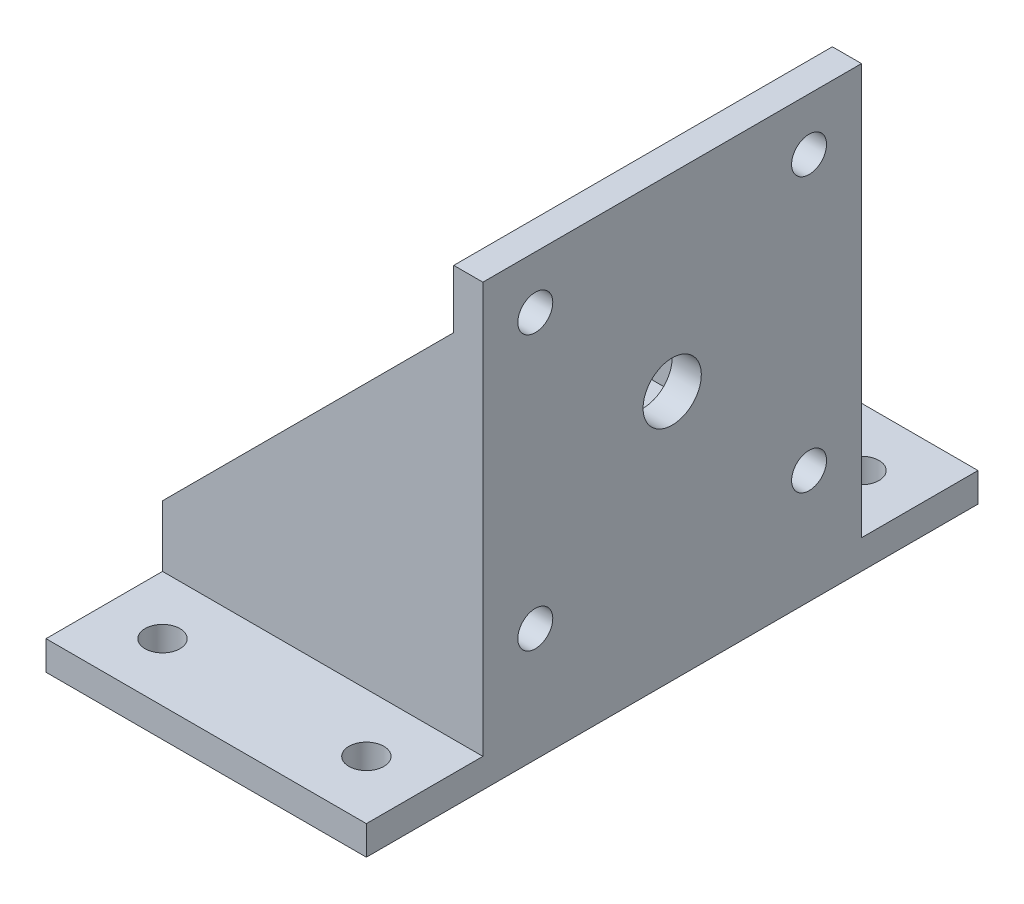
SolidWorks part; units mm, degrees
ref_plane "Front Plane" through (0, 0, 0) normal (0, 0, 1) x (1, 0, 0)
ref_plane "Top Plane" through (0, 0, 0) normal (0, 1, 0) x (1, 0, 0)
ref_plane "Right Plane" through (0, 0, 0) normal (1, 0, 0) x (0, 0, -1)
sketch "Sketch1" plane through (0, 0, 0) normal (0, 0, 1) x (1, 0, 0)
  line L0 (0, 0) -> (0, 60)
  line L1 (0, 60) -> (5, 60)
  line L2 (5, 60) -> (5, -15.5)
  line L3 (5, -15.5) -> (-50, -15.5)
  line L4 (-50, -15.5) -> (-50, 0)
  line L5 (-50, 0) -> (0, 0)
  dimension "D1" = 5
  dimension "D2" = 60
  dimension "D3" = 15.5
  dimension "D4" = 50
extrude "Boss-Extrude1" add sketch "Sketch1" along normal blind 65
sketch "Sketch2" plane through (0, 0, 0) normal (0, 0, -1) x (-1, 0, 0)
  line L0 (50, 0) -> (0, 50)
  line L6 (50, 0) -> (0, 0)
  line L7 (0, 0) -> (0, 60)
  line L8 (0, 60) -> (-5, 60)
  line L9 (-5, 60) -> (-5, -15.5)
  line L10 (-5, -15.5) -> (50, -15.5)
  line L11 (50, -15.5) -> (50, 0)
  line L12 (50, 0) -> (0, 0)
  line L13 (0, 0) -> (0, 60)
  line L14 (0, 60) -> (-5, 60)
  line L15 (-5, 60) -> (-5, -15.5)
  line L16 (-5, -15.5) -> (50, -15.5)
  line L17 (50, -15.5) -> (50, 0)
  line M8 (50, 0) -> (0, 0)
  line M9 (0, 0) -> (0, 60)
  dimension "D2" = 45
  dimension "D1" = 0
extrude "Boss-Extrude2" add sketch "Sketch2" against normal blind 5 contours M9 M8 region at (-16.6667, 16.6667, 0)
sketch "Sketch3" plane through (0, 0, 65) normal (0, 0, 1) x (1, 0, 0)
  line L3 (0, 50) -> (-50, 0)
  line L4 (-50, 0) -> (0, 0)
  line L5 (0, 0) -> (0, 50)
  line L7 (-50, 0) -> (0, 0)
  line L8 (0, 0) -> (0, 50)
  line L9 (0, 50) -> (-50, 0)
  dimension "D1" = 0
extrude "Boss-Extrude3" add sketch "Sketch3" against normal blind 5
sketch "Sketch4" plane through (0, 0, 0) normal (-1, 0, 0) x (0, 0, 1)
  line L0 (32.5, 60) -> (32.5, 0)
  line L2 (9, 4) -> (56, 4)
  line L3 (9, 4) -> (9, 51)
  line L4 (5, 0) -> (60, 0)
  line L5 (60, 0) -> (60, 50)
  line L6 (65, 60) -> (0, 60)
  line L7 (60, 50) -> (65, 50)
  line L8 (5, 0) -> (60, 0)
  line L9 (60, 0) -> (60, 50)
  line L10 (65, 60) -> (0, 60)
  line L12 (9, 51) -> (56, 51)
  line L13 (56, 4) -> (56, 51)
  line L14 (9, 4) -> (56, 51) construction
  line L15 (60, 50) -> (65, 50)
  line L16 (65, 50) -> (65, 60)
  line L17 (65, 50) -> (65, 60)
  line L18 (0, 60) -> (0, 50)
  line L19 (0, 60) -> (0, 50)
  line L20 (9, 51) -> (56, 4) construction
  line L22 (5, 50) -> (5, 0)
  line L23 (5, 50) -> (5, 0)
  line L24 (0, 50) -> (5, 50)
  line L25 (0, 50) -> (5, 50)
  circle A0 centre (32.5, 27.5) radius 5
  circle A1 centre (9, 51) radius 3
  circle A2 centre (56, 51) radius 3
  circle A3 centre (56, 4) radius 3
  circle A4 centre (9, 4) radius 3
  dimension "D2" = 10
  dimension "D4" = 6
  dimension "D3" = 47
  dimension "D5" = 27.5
  dimension "D1" = 0
extrude "Cut-Extrude1" cut sketch "Sketch4" against normal through all contours A0 | A1 | A2 | A3 | A4
sketch "Sketch5" plane through (0, -15.5, 0) normal (0, -1, 0) x (1, 0, 0)
  line L0 (-50, -20) -> (5, -20)
  line L1 (5, 85) -> (-50, 85)
  line L4 (-50, 0) -> (5, 0)
  line L5 (5, 0) -> (5, 65)
  line L6 (5, 65) -> (-50, 65)
  line L7 (-50, 65) -> (-50, 0)
  line L8 (-50, 0) -> (5, 0)
  line L9 (5, -20) -> (5, 85)
  line L10 (5, 65) -> (-50, 65)
  line L11 (-50, 85) -> (-50, -20)
  line M5 (-50, 0) -> (5, 0)
  line M7 (5, 65) -> (-50, 65)
  dimension "D1" = 0
  dimension "D2" = 20
  dimension "D3" = 20
extrude "Boss-Extrude4" add sketch "Sketch5" against normal blind 5 contours L11 L0 L9 M5 | L1 L11 L9 M7 region at (-22.5, -15.5, -10) region at (-22.5, -15.5, 75)
sketch "Sketch6" plane through (0, -10.5, 0) normal (0, 1, 0) x (1, 0, 0)
  line L0 (5, 10) -> (-50, 10) construction
  line L4 (-50, 0) -> (5, 0)
  line L5 (5, 0) -> (5, 20)
  line L6 (5, 20) -> (-50, 20)
  line L7 (-50, 20) -> (-50, 0)
  line L8 (-50, 0) -> (5, 0)
  line L9 (5, 0) -> (5, 20)
  line L10 (5, 20) -> (-50, 20)
  line L11 (-50, 20) -> (-50, 0)
  line L13 (0, -32.5) -> (-50, -32.5) construction
  line L17 (-50, -60) -> (0, -60)
  line L18 (0, -60) -> (0, -5)
  line L19 (0, -5) -> (-50, -5)
  line L20 (-50, -5) -> (-50, -60)
  line L21 (-50, -60) -> (0, -60)
  line L22 (0, -60) -> (0, -5)
  line L23 (0, -5) -> (-50, -5)
  line L24 (-50, -5) -> (-50, -60)
  circle A0 centre (-5, 10) radius 3
  circle A1 centre (-40, 10) radius 3
  circle A2 centre (-5, -75) radius 3
  circle A3 centre (-40, -75) radius 3
  dimension "D2" = 6
  dimension "D3" = 10
  dimension "D4" = 10
  dimension "D1" = 0
  dimension "D5" = 0
extrude "Cut-Extrude2" cut sketch "Sketch6" against normal blind 5 contours A1 | A0 | A2 | A3
sketch "Sketch8" plane through (-50, 0, 0) normal (-1, 0, 0) x (0, 0, 1)
  line L0 (60, -5) -> (5, -5)
  line L1 (5, -5) -> (5, -5)
  line L2 (5, -5) -> (5, -15.5)
  line L3 (5, -10.5) -> (5, -10.5)
  line L4 (5, -10.5) -> (5, -10.5)
  line L6 (60, -10.5) -> (60, -10.5)
  line L7 (60, -10.5) -> (60, -10.5)
  line L8 (60, -15.5) -> (60, -5)
  line L9 (60, -5) -> (60, -5)
  line L10 (0, 0) -> (0, -10.5)
  line L11 (0, -10.5) -> (-20, -10.5)
  line L12 (-20, -10.5) -> (-20, -15.5)
  line L13 (-20, -15.5) -> (85, -15.5)
  line L14 (85, -15.5) -> (85, -10.5)
  line L15 (85, -10.5) -> (65, -10.5)
  line L16 (65, -10.5) -> (65, 0)
  line L17 (65, 0) -> (60, 0)
  line L18 (60, 0) -> (5, 0)
  line L19 (5, 0) -> (0, 0)
  line L20 (0, 0) -> (0, -10.5)
  line L21 (0, -10.5) -> (-20, -10.5)
  line L22 (-20, -10.5) -> (-20, -15.5)
  line L23 (-20, -15.5) -> (85, -15.5)
  line L24 (85, -15.5) -> (85, -10.5)
  line L25 (85, -10.5) -> (65, -10.5)
  line L26 (65, -10.5) -> (65, 0)
  line L27 (65, 0) -> (60, 0)
  line L28 (60, 0) -> (5, 0)
  line L29 (5, 0) -> (0, 0)
  line L30 (5, -5) -> (5, -10.5) construction
  line L31 (60, -10.5) -> (60, -5) construction
  line L32 (5, -10.5) -> (60, -10.5) construction
  line M14 (-20, -15.5) -> (85, -15.5)
  dimension "D1" = 0
  dimension "D2" = 5
extrude "Cut-Extrude4" cut sketch "Sketch8" against normal offset from surface (50 mm away) 5 contours L8 L0 L2 M14 region at (-50, -10.25, 32.5) up to face at (5, 1, 9)
